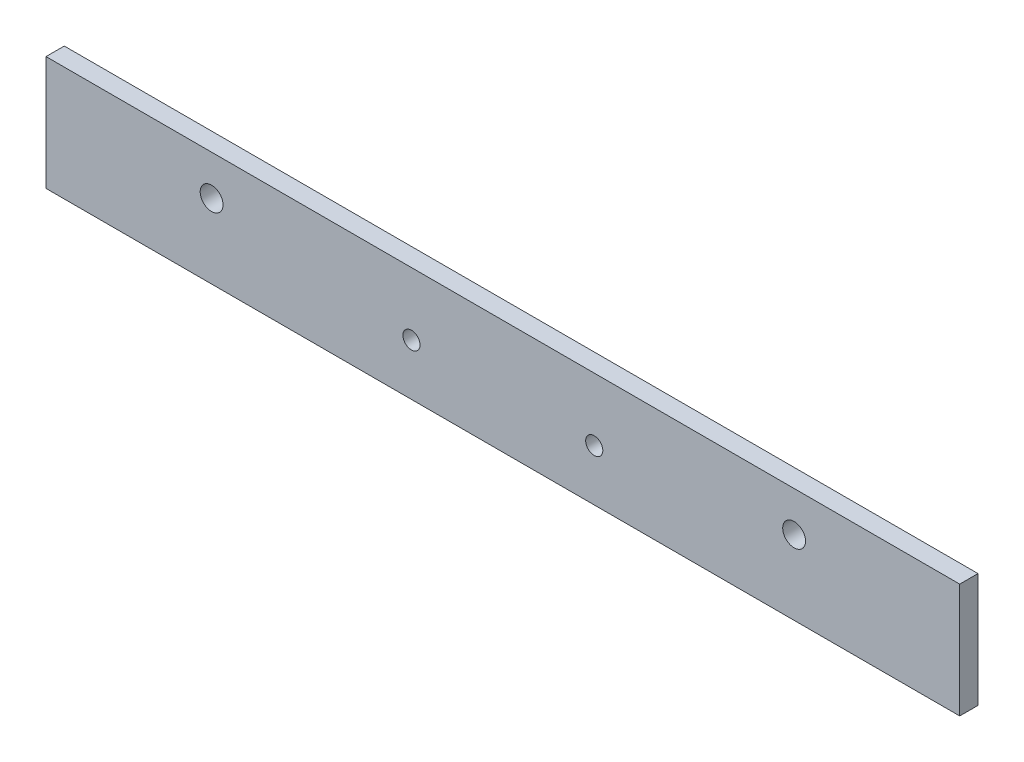
SolidWorks part; units mm, degrees
material "Balsa"
ref_plane "Front Plane" through (0, 0, 0) normal (0, 0, 1) x (1, 0, 0)
ref_plane "Top Plane" through (0, 0, 0) normal (0, 1, 0) x (1, 0, 0)
ref_plane "Right Plane" through (0, 0, 0) normal (1, 0, 0) x (0, 0, -1)
ref_plane "Plane1" through (0, 0, 10) normal (0, 0, 1) x (1, 0, 0)
sketch "Sketch2" plane through (0, -10, 10) normal (0, 0, -1) x (1, 0, 0)
  line L1 (0, -10) -> (160, -10)
  line L2 (0, -10) -> (0, 10)
  line L3 (0, 10) -> (160, 10)
  line L4 (160, -10) -> (160, 10)
  dimension "D1" = 20
  dimension "D2" = 160
extrude "Boss-Extrude1" add sketch "Sketch2" along normal blind 3.2
sketch "Sketch4" plane through (0, 0, 0) normal (0, 1, 0) x (1, 0, 0)
  line L0 (0, -10) -> (160, -10) construction
  line L1 (0, -6.8) -> (80, -6.8)
  line L2 (0, -6.8) -> (0, -10)
  line L3 (0, -10) -> (80, -10)
  line L4 (80, -6.8) -> (80, -10)
  line L5 (160, -6.8) -> (160, -10) construction
  dimension "D1" = 80
  dimension "D2" = 80
sketch "Sketch5" plane through (0, 0, 10) normal (0, 0, 1) x (1, 0, 0)
  line L0 (102, 2.15) -> (102, -20)
  line L1 (102, 0) -> (102, 4.3) construction
  line L2 (160, -20) -> (0, -20) construction
  line L3 (58, 2.15) -> (58, -20)
  line L4 (58, 0) -> (58, 4.3) construction
  line L7 (29, -7) -> (131, -7)
  line L9 (0, 0) -> (160, 0) construction
  circle A0 centre (131, -7) radius 2
  circle A1 centre (29, -7) radius 2
  dimension "D1" = 7
extrude "Cut-Extrude1" cut sketch "Sketch5" against normal through all both and the other way through all contours A0 | A1
sketch "Sketch6" plane through (0, 0, 10) normal (0, 0, 1) x (1, 0, 0)
  circle A0 centre (96, -11) radius 1.5
  circle A1 centre (64, -11) radius 1.5
  dimension "D1" = 32
extrude "Cut-Extrude2" cut sketch "Sketch6" against normal blind 10
